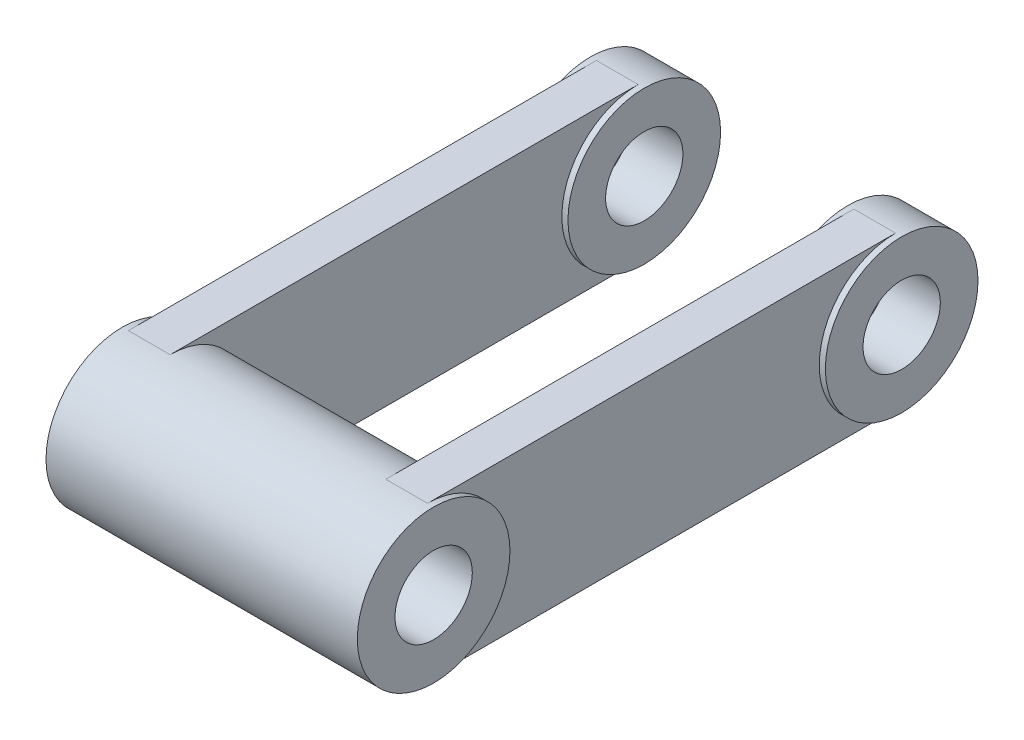
SolidWorks part; units mm, degrees
ref_plane "Front Plane" through (0, 0, 0) normal (0, 0, 1) x (1, 0, 0)
ref_plane "Top Plane" through (0, 0, 0) normal (0, 1, 0) x (1, 0, 0)
ref_plane "Right Plane" through (0, 0, 0) normal (1, 0, 0) x (0, 0, -1)
sketch "Sketch1" plane through (0, 0, 0) normal (1, 0, 0) x (0, 0, -1)
  circle A0 centre (0, 0) radius 75
  circle A1 centre (0, 0) radius 38
  dimension "D1" = 150
  dimension "D2" = 76
extrude "Boss-Extrude1" add sketch "Sketch1" along normal mid plane 306
ref_plane "Plane1" through (126.5, 0, 0) normal (1, 0, 0) x (0, 0, -1)
sketch "Sketch3" plane through (126.5, 0, 0) normal (1, 0, 0) x (0, 0, -1)
  line L0 (0, 75) -> (460, 75)
  line L2 (460, -75) -> (0, -75)
  arc A0 (0, 75) -> (0, -75) centre (0, 0) ccw
  arc A1 (460, -75) -> (460, 75) centre (460, 0) ccw
  circle A2 centre (460, 0) radius 38
  circle A4 centre (0, 0) radius 75 construction
  circle A6 centre (0, 0) radius 38 construction
  circle A7 centre (0, 0) radius 38
  dimension "D2" = 76
  dimension "D1" = 460
extrude "Boss-Extrude2" add sketch "Sketch3" along normal mid plane 41
sketch "Sketch5" plane through (126.5, 0, 0) normal (1, 0, 0) x (0, 0, -1)
  circle A1 centre (460, 0) radius 75
  circle A3 centre (460, 0) radius 38 construction
  circle A4 centre (460, 0) radius 38
  dimension "D1" = 150
extrude "Boss-Extrude3" add sketch "Sketch5" along normal mid plane 53
mirror "Mirror3" about plane through (0, 0, 0) normal (1, 0, 0) of "Boss-Extrude3", "Boss-Extrude2"
